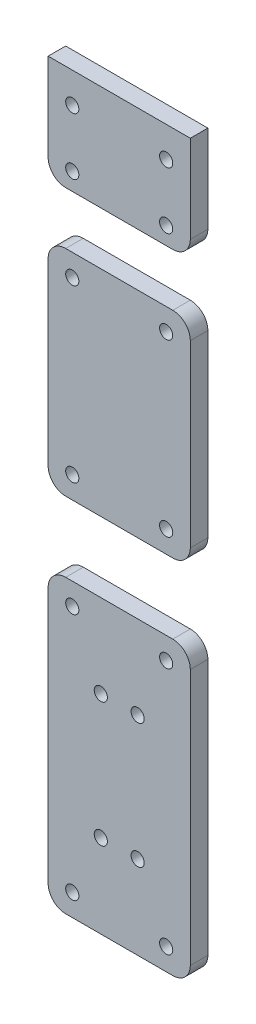
SolidWorks part; units mm, degrees
ref_plane "Front Plane" through (0, 0, 0) normal (0, 0, 1) x (1, 0, 0)
ref_plane "Top Plane" through (0, 0, 0) normal (0, 1, 0) x (1, 0, 0)
ref_plane "Right Plane" through (0, 0, 0) normal (1, 0, 0) x (0, 0, -1)
sketch "Sketch1" plane through (0, 0, 0) normal (0, 0, 1) x (1, 0, 0)
  line L0 (16.2, 1.5) -> (16.2, 14) construction
  line L1 (16.2, 109.64) -> (0, 109.64)
  line L2 (0, 109.64) -> (0, 99.66)
  line L3 (0, 1.5) -> (16.2, 1.5) construction
  line L4 (14.2, 59.21) -> (12.2, 59.21)
  line L5 (0, 14) -> (4, 14) construction
  line L6 (2, 26) -> (4, 26)
  line L7 (2, 91.66) -> (2.75, 91.66)
  line L8 (2, 67.21) -> (4, 67.21)
  line L9 (8.1, 109.64) -> (8.1, 97.66) construction
  line L10 (0, 14) -> (0, 1.5) construction
  line L11 (2, 97.66) -> (2.75, 97.66)
  line L12 (16.2, 28) -> (16.2, 57.21)
  line L13 (16.2, 99.66) -> (16.2, 109.64)
  line L14 (0, 89.66) -> (0, 69.21)
  line L15 (0, 57.21) -> (0, 28)
  line L16 (16.2, 69.21) -> (16.2, 89.66)
  line L17 (6, 14) -> (6, 26)
  line L18 (4, 59.21) -> (4, 67.21)
  line L19 (4, 14) -> (4, 26)
  line L20 (6, 59.21) -> (6, 67.21)
  line L21 (4, 91.66) -> (4, 97.66)
  line L22 (2.75, 97.66) -> (2.75, 91.66)
  line L23 (10.2, 14) -> (10.2, 26)
  line L24 (12.2, 14) -> (12.2, 26)
  line L25 (10.2, 59.21) -> (10.2, 67.21)
  line L26 (12.2, 59.21) -> (12.2, 67.21)
  line L27 (13.45, 91.66) -> (13.45, 97.66)
  line L28 (12.2, 91.66) -> (12.2, 97.66)
  line L29 (4, 97.66) -> (12.2, 97.66)
  line L30 (4, 91.66) -> (12.2, 91.66)
  line L31 (13.45, 91.66) -> (14.2, 91.66)
  line L32 (13.45, 97.66) -> (14.2, 97.66)
  line L33 (6, 67.21) -> (10.2, 67.21)
  line L34 (12.2, 67.21) -> (14.2, 67.21)
  line L35 (10.2, 59.21) -> (6, 59.21)
  line L36 (4, 59.21) -> (2, 59.21)
  line L37 (6, 14) -> (10.2, 14) construction
  line L38 (6, 26) -> (10.2, 26)
  line L39 (12.2, 26) -> (14.2, 26)
  line L40 (12.2, 14) -> (16.2, 14) construction
  line L41 (12.2, 14) -> (10.2, 14)
  line L42 (6, 14) -> (4, 14)
  circle A0 centre (13.45, 56.71) radius 0.75
  circle A1 centre (10.2, 49.71) radius 0.75
  circle A2 centre (13.45, 106.16) radius 0.75
  circle A3 centre (2.75, 99.66) radius 0.75
  circle A4 centre (6, 49.71) radius 0.75
  circle A5 centre (2.75, 28.5) radius 0.75
  circle A6 centre (2.75, 89.16) radius 0.75
  circle A7 centre (2.75, 56.71) radius 0.75
  circle A8 centre (13.45, 89.16) radius 0.75
  circle A9 centre (13.45, 99.66) radius 0.75
  arc A10 (16.2, 28) -> (14.2, 26) centre (14.2, 28) cw
  arc A11 (0, 28) -> (2, 26) centre (2, 28) ccw
  arc A12 (16.2, 57.21) -> (14.2, 59.21) centre (14.2, 57.21) ccw
  arc A13 (0, 57.21) -> (2, 59.21) centre (2, 57.21) cw
  arc A14 (16.2, 69.21) -> (14.2, 67.21) centre (14.2, 69.21) cw
  arc A15 (0, 69.21) -> (2, 67.21) centre (2, 69.21) ccw
  arc A16 (0, 89.66) -> (2, 91.66) centre (2, 89.66) cw
  arc A17 (16.2, 89.66) -> (14.2, 91.66) centre (14.2, 89.66) ccw
  arc A18 (16.2, 99.66) -> (14.2, 97.66) centre (14.2, 99.66) cw
  arc A19 (2, 97.66) -> (0, 99.66) centre (2, 99.66) cw
  circle A28 centre (13.45, 69.71) radius 0.75
  circle A29 centre (6, 35.5) radius 0.75
  circle A32 centre (2.75, 106.16) radius 0.75
  circle A33 centre (10.2, 35.5) radius 0.75
  circle A34 centre (2.75, 69.71) radius 0.75
  circle A35 centre (13.45, 28.5) radius 0.75
  circle A36 centre (2.85, 11.5) radius 0.75 construction
  circle A37 centre (13.35, 11.5) radius 0.75 construction
  circle A38 centre (13.35, 5.5) radius 0.75 construction
  circle A39 centre (2.85, 5.5) radius 0.75 construction
  point P71 (16.2, 26)
  point P74 (0, 26)
  point P91 (16.2, 59.21)
  point P94 (0, 59.21)
  point P97 (16.2, 67.21)
  point P100 (0, 67.21)
  point P103 (0, 91.66)
  point P106 (16.2, 91.66)
  point P109 (16.2, 97.66)
  point P112 (0, 97.66)
  dimension "D1" = 4
  dimension "D45" = 1.5
  dimension "D46" = 2
  dimension "D2" = 4
  dimension "D3" = 2.85
  dimension "D4" = 2.85
  dimension "D5" = 16.2
  dimension "D6" = 6
  dimension "D7" = 6
  dimension "D8" = 2.85
  dimension "D9" = 2.85
  dimension "D10" = 2.5
  dimension "D11" = 12
  dimension "D12" = 33.21
  dimension "D13" = 2.5
  dimension "D14" = 2.5
  dimension "D15" = 2.75
  dimension "D16" = 2.75
  dimension "D17" = 2.5
  dimension "D18" = 2.5
  dimension "D19" = 2.75
  dimension "D20" = 2.75
  dimension "D21" = 9.5
  dimension "D22" = 6
  dimension "D23" = 9.5
  dimension "D24" = 6
  dimension "D25" = 9.5
  dimension "D26" = 9.5
  dimension "D27" = 6
  dimension "D28" = 6
  dimension "D29" = 8
  dimension "D30" = 24.45
  dimension "D31" = 2.5
  dimension "D32" = 2.5
  dimension "D33" = 2.75
  dimension "D34" = 2.75
  dimension "D35" = 6
  dimension "D36" = 2.75
  dimension "D37" = 2
  dimension "D38" = 2.75
  dimension "D39" = 8.5
  dimension "D40" = 11.98
  dimension "D41" = 2.5
  dimension "D42" = 2.5
  dimension "D43" = 2.75
  dimension "D44" = 2.75
extrude "Boss-Extrude1" add sketch "Sketch1" along normal blind 2
sketch "Sketch2" plane through (0, 0, 0) normal (0, 0, -1) x (-1, 0, 0)
  line L0 (-13.45, 97.66) -> (-2.75, 97.66)
  line L1 (-2.75, 97.66) -> (-2.75, 91.66)
  line L2 (-2.75, 91.66) -> (-13.45, 91.66)
  line L3 (-13.45, 91.66) -> (-13.45, 97.66)
  line L4 (-12.2, 67.21) -> (-4, 67.21)
  line L5 (-4, 67.21) -> (-4, 59.21)
  line L6 (-4, 59.21) -> (-12.2, 59.21)
  line L7 (-12.2, 59.21) -> (-12.2, 67.21)
  line L8 (-12.2, 26) -> (-4, 26)
  line L9 (-4, 26) -> (-4, 14)
  line L10 (-4, 14) -> (-12.2, 14)
  line L11 (-12.2, 14) -> (-12.2, 26)
extrude "Cut-Extrude1" cut sketch "Sketch2" against normal up to surface (2 mm away) up to face at (3.5, 69.71, 2)
equation "\"D12@Sketch1\"= \"HL@parametersSketch@prostheticParameters.SLDPRT\" * 0.266 - 12 - 4 'Middle PIP Length"
equation "\"D30@Sketch1\"= \"HL@parametersSketch@prostheticParameters.SLDPRT\" * 0.17 - 4 - 3'Middle MIP Length"
equation "\"D5@Sketch1\"= \"fingerWidth@parametersSketch@prostheticParameters.SLDPRT\" 'Middle Width"
equation "\"D40@Sketch1\"= \"HL@parametersSketch@prostheticParameters.SLDPRT\" * 0.108 - 3 - 5'Middle DIP Length"
